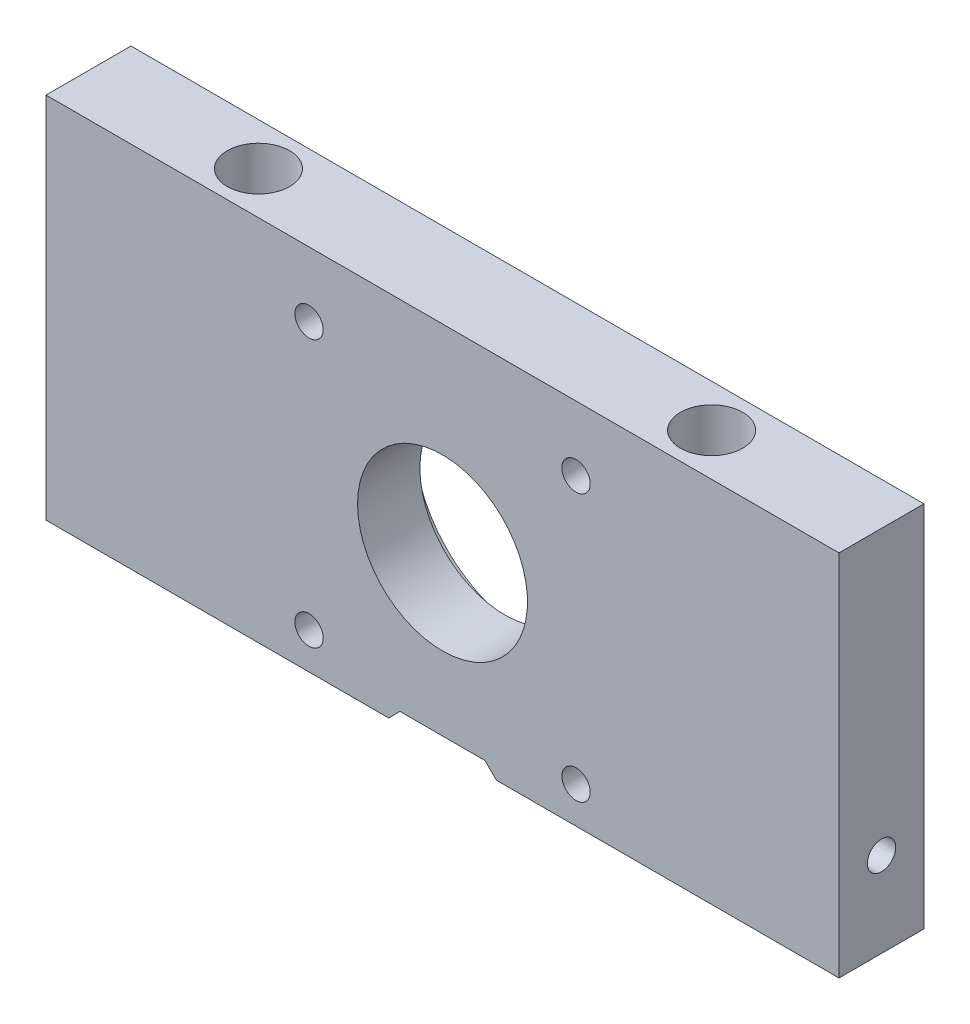
SolidWorks part; units mm, degrees
material "6061 Alloy"
ref_plane "Ön Düzlem" through (0, 0, 0) normal (0, 0, 1) x (1, 0, 0)
ref_plane "Üst Düzlem" through (0, 0, 0) normal (0, 1, 0) x (1, 0, 0)
ref_plane "Sağ Düzlem" through (0, 0, 0) normal (1, 0, 0) x (0, 0, -1)
sketch "Sketch1" plane through (0, 0, 0) normal (0, 0, 1) x (1, 0, 0)
  line L1 (-70, 32.5) -> (70, 32.5)
  line L2 (-70, 32.5) -> (-70, -32.5)
  line L3 (-70, -32.5) -> (70, -32.5)
  line L4 (70, 32.5) -> (70, -32.5)
  line L5 (-70, 32.5) -> (70, -32.5) construction
  line L6 (-70, -32.5) -> (70, 32.5) construction
  point P0 (0, 0)
  dimension "D1" = 65
  dimension "D2" = 140
extrude "Boss-Extrude1" add sketch "Sketch1" along normal blind 15
sketch "Sketch2" plane through (0, 0, 15) normal (0, 0, -1) x (-1, 0, 0)
  line L0 (0, -2.5) -> (0, 32.5) construction
  line L1 (0, -2.5) -> (24, -2.5) construction
  line L2 (-70, 32.5) -> (70, 32.5) construction
  line L4 (-23.57, 21.07) -> (23.57, 21.07) construction
  line L5 (-23.57, 21.07) -> (-23.57, -26.07) construction
  line L6 (-23.57, -26.07) -> (23.57, -26.07) construction
  line L7 (23.57, 21.07) -> (23.57, -26.07) construction
  line L8 (-23.57, 21.07) -> (23.57, -26.07) construction
  line L9 (-23.57, -26.07) -> (23.57, 21.07) construction
  circle A0 centre (0, -2.5) radius 15
  circle A3 centre (-23.57, 21.07) radius 2.5
  circle A4 centre (23.57, 21.07) radius 2.5
  circle A5 centre (23.57, -26.07) radius 2.5
  circle A6 centre (-23.57, -26.07) radius 2.5
  dimension "D1" = 35
  dimension "D2" = 47.14
  dimension "D4" = 30
  dimension "D5" = 5
  dimension "D3" = 47.14
extrude "Cut-Extrude2" cut sketch "Sketch2" along normal blind 27
sketch "Sketch7" plane through (70, 0, 0) normal (1, 0, 0) x (0, 0, -1)
  line L0 (-7.5, 32.5) -> (-7.5, 22.5) construction
  line L1 (-15, 32.5) -> (0, 32.5) construction
  line L2 (-16.5, 22.5) -> (1.5, 22.5) construction
  point P7 (-7.5, 22.5)
  dimension "D1" = 10
  dimension "D2" = 18
sketch "Sketch13" plane through (70, 0, 0) normal (1, 0, 0) x (0, 0, -1)
  line L0 (-7.5, -32.5) -> (-7.5, -17.5) construction
  line L1 (-15, -32.5) -> (0, -32.5) construction
  dimension "D1" = 15
hole_wizard "Tap Drill for M6 Tap1" positions "Sketch14" profile "Sketch15" hole size "M6" standard "ISO"
sketch "Sketch14" plane through (70, 0, 0) normal (1, 0, 0) x (0, 0, -1)
  point P0 (-7.5, -17.5)
sketch "Sketch15" plane through (70, -17.5, 7.5) normal (0, 1, 0) x (0, 0, -1)
  line L0 (0, 0) -> (0, 16.5022)
  line L1 (0, 16.5022) -> (2.5, 15)
  line L2 (2.5, 15) -> (2.5, 0)
  line L5 (2.5, 0) -> (0, 0)
  line L10 (0, 16.5022) -> (-2.5, 15) construction
  line L11 (0, -6.35) -> (0, 107.95) construction
  dimension "Hole Dia." = 5
  dimension "Hole Depth" = 15
  dimension "Drill Angle" = 118
hole_wizard "CBORE for M6 Hex Socket Head Cap Screw3" positions "Sketch23" profile "Sketch24" counterbore size "M6" standard "ISO" end condition through all
sketch "Sketch23" plane through (0, 32.5, 0) normal (0, 1, 0) x (1, 0, 0)
  line L1 (-70, 0) -> (70, -15) construction
  line L3 (-70, -15) -> (70, 0) construction
  line L5 (70, -7.5) -> (-70, -7.5) construction
  line L6 (70, -15) -> (70, 0) construction
  line L7 (-70, -15) -> (-70, 0) construction
  point P0 (40, -7.5)
  point P3 (-40, -7.5)
  dimension "D1" = 80
sketch "Sketch24" plane through (40, 32.5, 7.5) normal (1, 0, 0) x (0, 0, 1)
  line L0 (0, 0) -> (0, 65)
  line L1 (0, 65) -> (3.3, 65)
  line L3 (3.3, 65) -> (3.3, 61.4)
  line L4 (3.3, 61.4) -> (5.5, 61.4)
  line L5 (5.5, 61.4) -> (5.5, 0)
  line L7 (5.5, 0) -> (0, 0)
  line L11 (0, -6.35) -> (0, 107.95) construction
  dimension "Thru Hole Dia." = 6.6
  dimension "Thru Hole Depth" = 65
  dimension "C'Bore Dia." = 11
  dimension "C'Bore Depth" = 61.4
sketch "Sketch29" plane through (0, 0, 15) normal (0, 0, 1) x (1, 0, 0)
  line L0 (-70, -32.5) -> (70, -32.5) construction
  line L2 (-17.5, -30.5) -> (17.5, -30.5)
  line L3 (-17.5, -30.5) -> (-17.5, -32.5)
  line L4 (-17.5, -32.5) -> (17.5, -32.5)
  line L5 (17.5, -30.5) -> (17.5, -32.5)
  point P0 (0, -32.5)
  dimension "D1" = 2
  dimension "D2" = 35
extrude "Cut-Extrude6" cut sketch "Sketch29" against normal through all
chamfer "Chamfer2" distance 10 angle 45 2 edges at (-17.5, -30.5, 7.5) (17.5, -30.5, 7.5)
sketch "Sketch30" plane through (0, 0, 0) normal (0, 0, -1) x (-1, 0, 0)
  line L0 (0, 32.5) -> (0, -50.208) construction
  line L1 (-70, 32.5) -> (70, 32.5) construction
  line L3 (-28.2, 32.5) -> (28.2, 32.5)
  line L4 (-28.2, 32.5) -> (-28.2, -32.5)
  line L5 (-28.2, -32.5) -> (28.2, -32.5)
  line L6 (28.2, 32.5) -> (28.2, -32.5)
  line L7 (-28.2, 32.5) -> (28.2, -32.5) construction
  line L8 (-28.2, -32.5) -> (28.2, 32.5) construction
  circle A1 centre (0, -2.5) radius 20
  point P9 (0, 0)
  dimension "D2" = 40
  dimension "D1" = 56.4
extrude "Cut-Extrude7" cut sketch "Sketch30" against normal blind 4 contours A1
